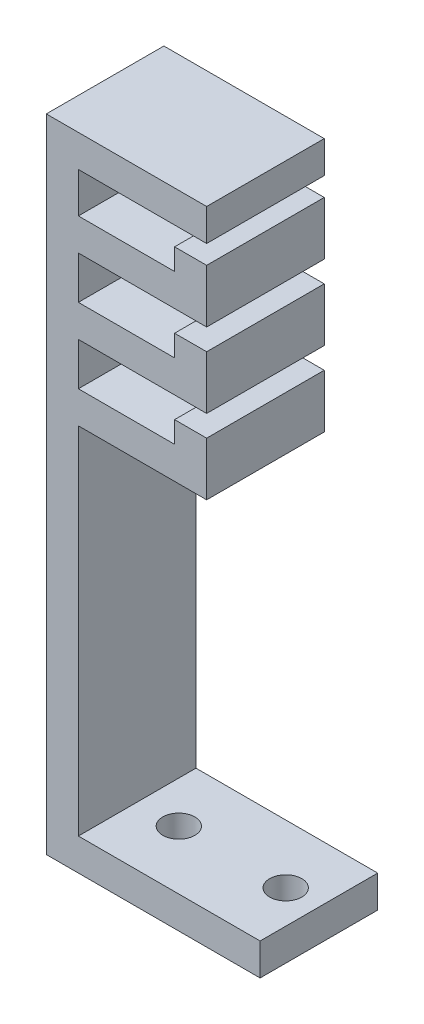
SolidWorks part; units mm, degrees
ref_plane "Front Plane" through (0, 0, 0) normal (0, 0, 1) x (1, 0, 0)
ref_plane "Top Plane" through (0, 0, 0) normal (0, 1, 0) x (1, 0, 0)
ref_plane "Right Plane" through (0, 0, 0) normal (1, 0, 0) x (0, 0, -1)
sketch "Sketch1" plane through (0, 0, 0) normal (0, 0, 1) x (1, 0, 0)
  line L0 (0, 0) -> (-20, 0)
  line L1 (-20, 0) -> (-20, 60)
  line L2 (0, 0) -> (0, 3)
  line L3 (0, 3) -> (-17, 3)
  line L4 (-17, 3) -> (-17, 36.2329)
  line L5 (-17, 36.2329) -> (-5, 36.2329)
  line L6 (-5, 36.2329) -> (-5, 41.2329)
  line L7 (-5, 41.2329) -> (-8, 41.2329)
  line L8 (-8, 41.2329) -> (-8, 39.2329)
  line L9 (-8, 39.2329) -> (-17, 39.2329)
  line L18 (-17, 39.2329) -> (-17, 43.2329)
  line L22 (-20, 60) -> (-17, 60)
  line L24 (-17, 43.2329) -> (-5, 43.2329)
  line L25 (-5, 43.2329) -> (-5, 48.2329)
  line L26 (-5, 48.2329) -> (-8, 48.2329)
  line L27 (-8, 48.2329) -> (-8, 46.2329)
  line L28 (-8, 46.2329) -> (-17, 46.2329)
  line L29 (-17, 50.2329) -> (-5, 50.2329)
  line L30 (-5, 50.2329) -> (-5, 55.2329)
  line L31 (-5, 55.2329) -> (-8, 55.2329)
  line L32 (-8, 55.2329) -> (-8, 53.2329)
  line L33 (-8, 53.2329) -> (-17, 53.2329)
  line L34 (-17, 36.2329) -> (-17, 43.2329) construction
  line L35 (-17, 60) -> (-5, 60)
  line L38 (-17, 57) -> (-17, 53.2329)
  line L39 (-17, 50.2329) -> (-17, 46.2329)
  line L40 (-17, 57) -> (-5, 57)
  line L41 (-5, 57) -> (-5, 60)
  point P3 (0, 1.5)
  dimension "D1" = 60
  dimension "D2" = 20
  dimension "D3" = 3
  dimension "D4" = 3
  dimension "D6" = 5
  dimension "D7" = 12
  dimension "D8" = 3
  dimension "D10" = 7
  dimension "D9" = 3
extrude "Boss-Extrude2" add sketch "Sketch1" along normal blind 11
sketch "Sketch4" plane through (0, 0, 0) normal (0, -1, 0) x (1, 0, 0)
  line L0 (-20, 11) -> (0, 11) construction
  circle A0 centre (-3.1033, 5.5) radius 1.5
  circle A2 centre (-13.1033, 5.5) radius 1.5
  point P2 (-3.1033, 5.5)
  dimension "D2" = 3
  dimension "D1" = 5.5
  dimension "D3" = 10
extrude "Cut-Extrude1" cut sketch "Sketch4" against normal blind 11
